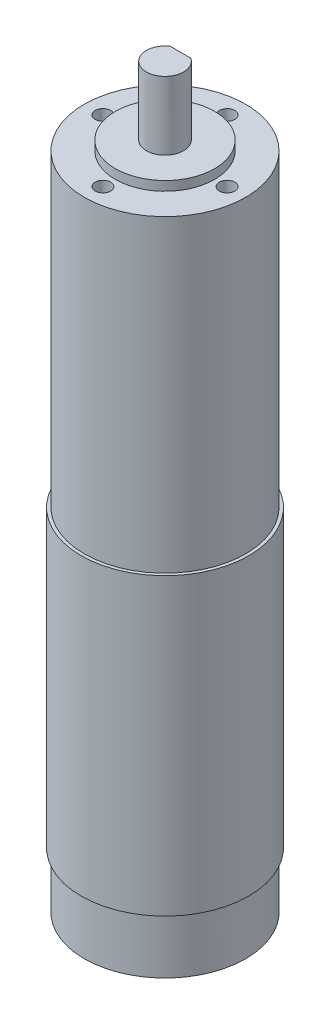
SolidWorks part; units mm, degrees
ref_plane "Front Plane" through (0, 0, 0) normal (0, 0, 1) x (1, 0, 0)
ref_plane "Top Plane" through (0, 0, 0) normal (0, 1, 0) x (1, 0, 0)
ref_plane "Right Plane" through (0, 0, 0) normal (1, 0, 0) x (0, 0, -1)
sketch "Sketch1" plane through (0, 0, 0) normal (0, 1, 0) x (1, 0, 0)
  circle A0 centre (0, 0) radius 27
  dimension "D1" = 54
extrude "Boss-Extrude1" add sketch "Sketch1" along normal blind 95
sketch "Sketch2" plane through (0, 95, 0) normal (0, 1, 0) x (1, 0, 0)
  circle A0 centre (0, 0) radius 26
  dimension "D1" = 52
extrude "Boss-Extrude2" add sketch "Sketch2" along normal blind 99.5
sketch "Sketch3" plane through (0, 194.5, 0) normal (0, 1, 0) x (1, 0, 0)
  circle A0 centre (0, 0) radius 16
  dimension "D1" = 32
extrude "Boss-Extrude3" add sketch "Sketch3" along normal blind 3
sketch "Sketch4" plane through (0, 197.5, 0) normal (0, 1, 0) x (1, 0, 0)
  circle A0 centre (0, 0) radius 6
  dimension "D1" = 12
extrude "Boss-Extrude4" add sketch "Sketch4" along normal blind 22
sketch "Sketch5" plane through (0, 219.5, 0) normal (0, 1, 0) x (1, 0, 0)
  line L0 (-3.3166, 5) -> (3.3166, 5)
  arc A0 (3.3166, 5) -> (-3.3166, 5) centre (0, 0) ccw
  circle A1 centre (0, 0) radius 6 construction
  dimension "D1" = 5
extrude "Cut-Extrude1" cut sketch "Sketch5" against normal blind 15
sketch "Sketch6" plane through (0, 194.5, 0) normal (0, 1, 0) x (1, 0, 0)
  circle A0 centre (0, 0) radius 20 construction
  circle A1 centre (0, 20) radius 2.5
  circle A2 centre (-20, 0) radius 2.5
  circle A3 centre (0, -20) radius 2.5
  circle A4 centre (20, 0) radius 2.5
  dimension "D1" = 40
  dimension "D2" = 5
  dimension "D3" = 5
  dimension "D4" = 5
  dimension "D5" = 5
extrude "Cut-Extrude2" cut sketch "Sketch6" against normal blind 10
sketch "Sketch7" plane through (0, 0, 0) normal (0, -1, 0) x (1, 0, 0)
  circle A0 centre (0, 0) radius 26
  dimension "D1" = 52
extrude "Boss-Extrude5" add sketch "Sketch7" along normal blind 18
